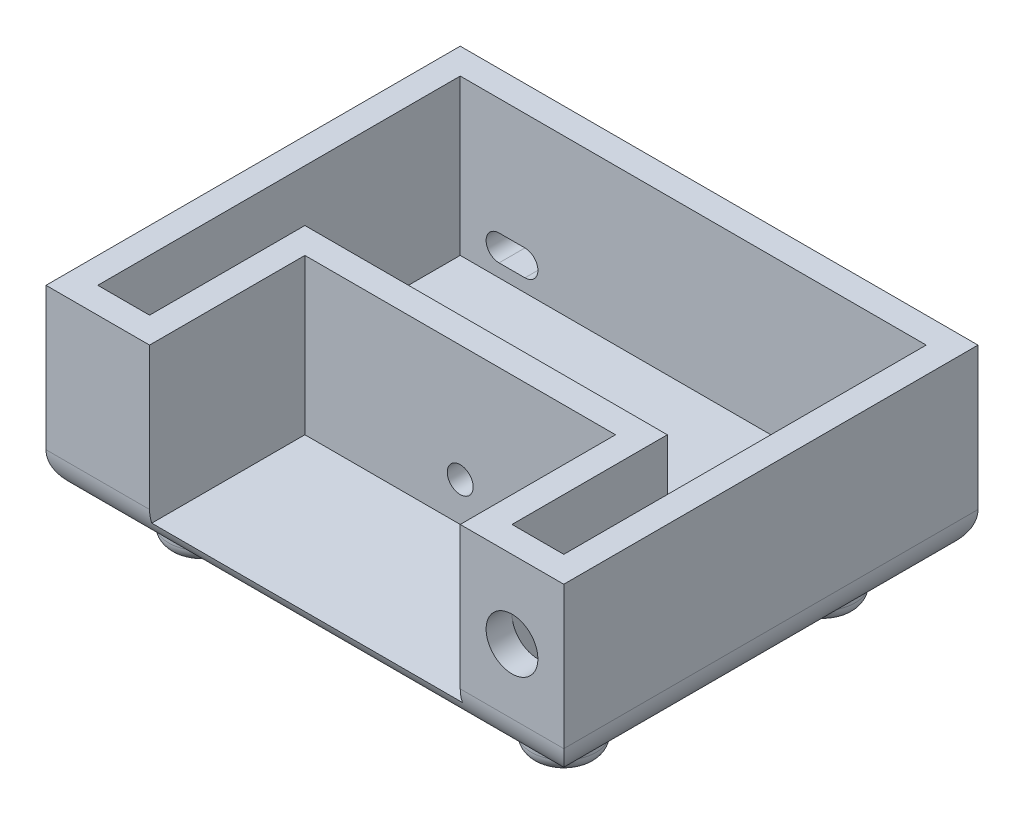
SolidWorks part; units mm, degrees
material "Teak"
ref_plane "Front Plane" through (0, 0, 0) normal (0, 0, 1) x (1, 0, 0)
ref_plane "Top Plane" through (0, 0, 0) normal (0, 1, 0) x (1, 0, 0)
ref_plane "Right Plane" through (0, 0, 0) normal (1, 0, 0) x (0, 0, -1)
sketch "Sketch2" plane through (0, 0, 0) normal (0, 1, 0) x (1, 0, 0)
  line L1 (-100, 80) -> (100, 80)
  line L2 (-100, 80) -> (-100, -80)
  line L3 (-100, -80) -> (100, -80)
  line L4 (100, 80) -> (100, -80)
  line L5 (-100, 80) -> (100, -80) construction
  line L6 (-100, -80) -> (100, 80) construction
  point P0 (0, 0)
  dimension "D1" = 200
  dimension "D2" = 160
extrude "Boss-Extrude1" add sketch "Sketch2" along normal blind 10
sketch "Sketch3" plane through (0, 10, 0) normal (0, 1, 0) x (1, 0, 0)
  line L0 (100, -80) -> (100, 80) construction
  line L1 (-100, 80) -> (100, 80)
  line L2 (-100, 80) -> (-100, -80)
  line L3 (-100, -80) -> (-60, -80)
  line L4 (100, 80) -> (100, -80)
  line L5 (-100, 80) -> (100, -80) construction
  line L6 (-100, -80) -> (100, 80) construction
  line L7 (-60, -80) -> (-60, -20)
  line L8 (-60, -20) -> (60, -20)
  line L9 (60, -20) -> (60, -80)
  line L10 (60, -80) -> (100, -80)
  line L11 (90, 70) -> (90, -70)
  line L12 (70, -70) -> (90, -70)
  line L13 (70, -10) -> (70, -70)
  line L14 (-70, -10) -> (70, -10)
  line L15 (-70, -70) -> (-70, -10)
  line L16 (-90, -70) -> (-70, -70)
  line L17 (-90, 70) -> (-90, -70)
  line L18 (-90, 70) -> (90, 70)
  point P1 (0, 0)
  dimension "D1" = 200
  dimension "D2" = 160
  dimension "D3" = 120
  dimension "D4" = 60
  dimension "D5" = 40
  dimension "D6" = 10
extrude "Boss-Extrude2" add sketch "Sketch3" along normal blind 60
sketch "Sketch7" plane through (0, 0, 20) normal (0, 0, 1) x (1, 0, 0)
  line L0 (60, 70) -> (60, 10) construction
  line L1 (-60, 10) -> (60, 10) construction
  circle A0 centre (0, 25) radius 5
  dimension "D1" = 10
  dimension "D2" = 60
  dimension "D3" = 15
sketch "Sketch8" plane through (0, 0, 0) normal (0, -1, 0) x (1, 0, 0)
  line L0 (100, 80) -> (100, -80) construction
  line L2 (-100, 80) -> (100, 80) construction
  line L3 (0, -52.25) -> (0, 52.25) construction
  line L4 (52.25, 0) -> (-52.25, 0) construction
  circle A0 centre (70, 50) radius 12.5
  circle A1 centre (-70, 50) radius 12.5
  circle A2 centre (70, -50) radius 12.5
  circle A3 centre (-70, -50) radius 12.5
  dimension "D1" = 25
  dimension "D2" = 30
  dimension "D3" = 30
extrude "Boss-Extrude6" add sketch "Sketch8" along normal blind 15
fillet "Fillet2" radius 5 4 edges at (70, -15, -37.5) (-70, -15, -62.5) (-70, -15, 62.5) (70, -15, 37.5)
sketch "Sketch9" plane through (0, 0, -80) normal (0, 0, -1) x (-1, 0, 0)
  line L0 (65, 20) -> (75, 20) construction
  line L1 (65, 25) -> (75, 25)
  line L2 (65, 15) -> (75, 15)
  line L3 (-100, 0) -> (100, 0) construction
  line L4 (100, 70) -> (100, 0) construction
  arc A0 (65, 25) -> (65, 15) centre (65, 20) ccw
  arc A1 (75, 15) -> (75, 25) centre (75, 20) ccw
  point P2 (70, 20)
  dimension "D2" = 5
  dimension "D1" = 10
  dimension "D3" = 20
  dimension "D4" = 30
extrude "Cut-Extrude4" cut sketch "Sketch9" against normal blind 15
sketch "Sketch10" plane through (0, 0, 80) normal (0, 0, 1) x (1, 0, 0)
  line L0 (100, 70) -> (100, 0) construction
  line L1 (-100, 0) -> (100, 0) construction
  circle A0 centre (80, 40) radius 10
  dimension "D1" = 20
  dimension "D2" = 20
  dimension "D3" = 40
extrude "Cut-Extrude5" cut sketch "Sketch10" against normal blind 10
extrude "Cut-Extrude6" cut sketch "Sketch7" against normal blind 10 contours A0
sketch "Sketch11" plane through (0, 0, 20) normal (0, 0, 1) x (1, 0, 0)
  line L0 (44.2374, 27.4038) -> (44.2374, 17.4038) construction
  line L1 (47.2374, 27.4038) -> (47.2374, 17.4038)
  line L2 (41.2374, 27.4038) -> (41.2374, 17.4038)
  arc A0 (47.2374, 27.4038) -> (41.2374, 27.4038) centre (44.2374, 27.4038) ccw
  arc A1 (41.2374, 17.4038) -> (47.2374, 17.4038) centre (44.2374, 17.4038) ccw
  point P2 (44.2374, 22.4038)
extrude "Cut-Extrude7" cut sketch "Sketch11" against normal blind 10
fillet "Fillet5" radius 15 4 edges at (0, 0, -80) (100, 0, 0) (0, 0, 80) (-100, 0, 0)
